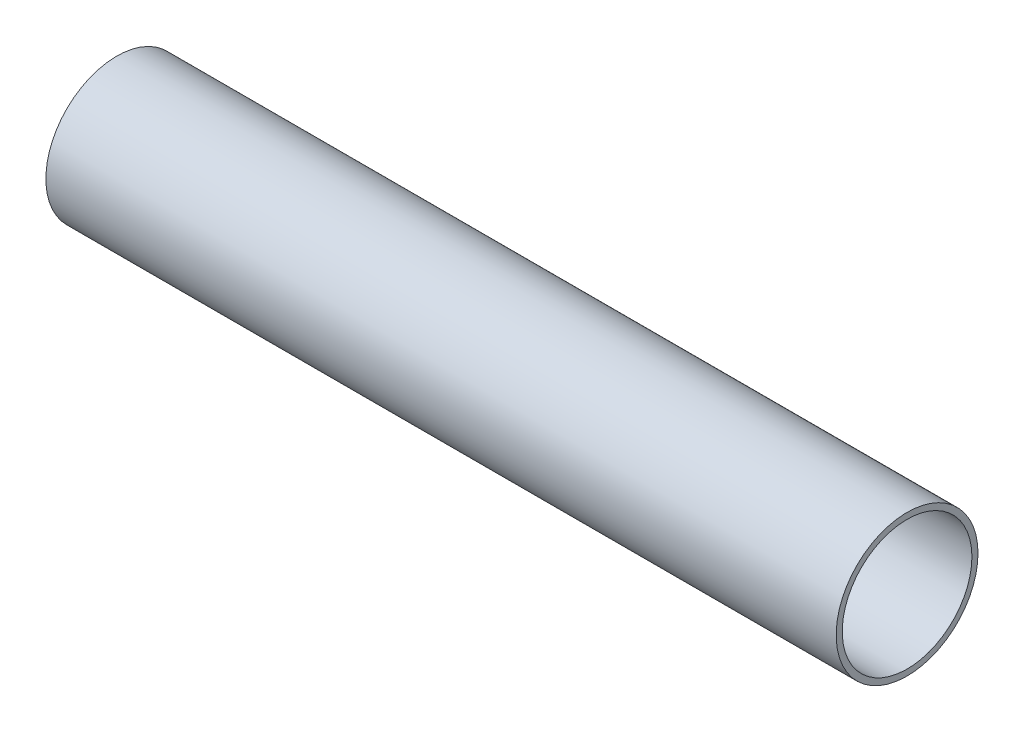
SolidWorks part; units mm, degrees
ref_plane "Alzado" through (0, 0, 0) normal (0, 0, 1) x (1, 0, 0)
ref_plane "Planta" through (0, 0, 0) normal (0, 1, 0) x (1, 0, 0)
ref_plane "Vista lateral" through (0, 0, 0) normal (1, 0, 0) x (0, 0, -1)
sketch "Croquis3" plane through (0, 0, 0) normal (1, 0, 0) x (0, 0, -1)
  circle A0 centre (0, 0) radius 3.5
  circle A1 centre (0, 0) radius 3.2
extrude "Saliente-Extruir1" add sketch "Croquis3" along normal blind 19.5 and the other way blind 19.5
